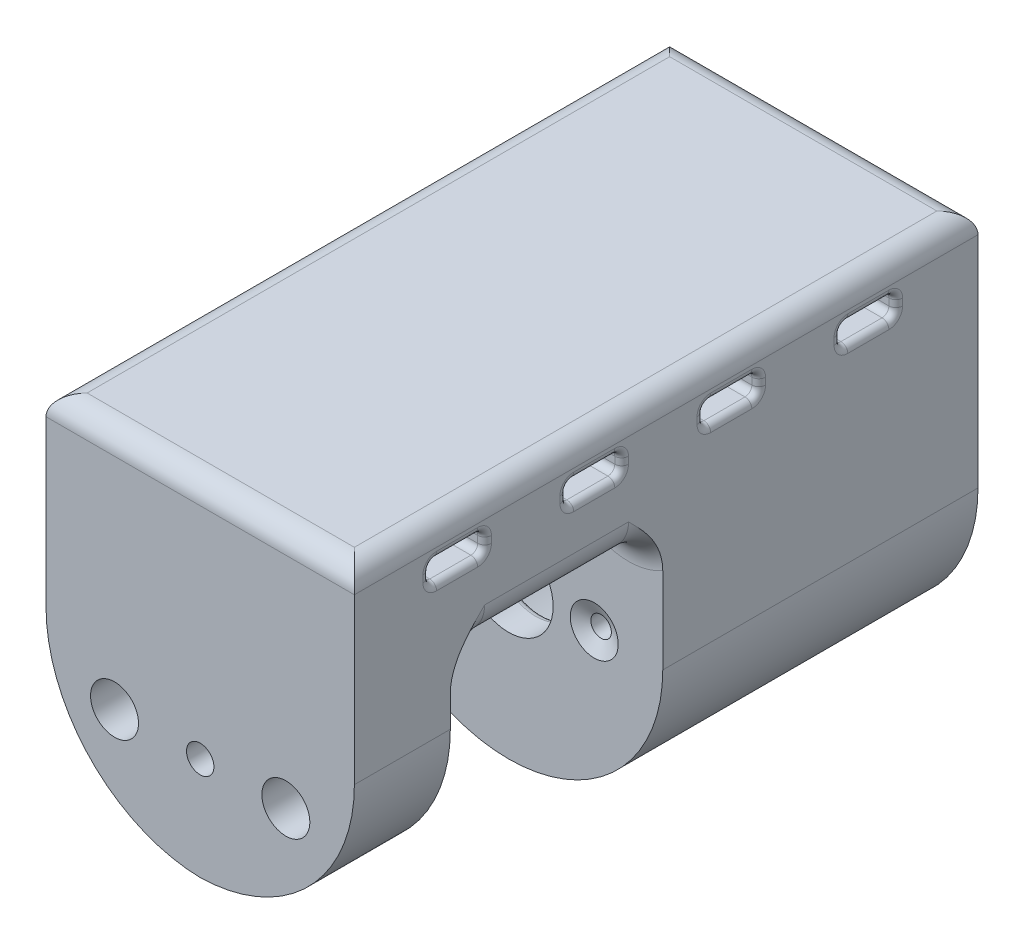
SolidWorks part; units mm, degrees
ref_plane "Płaszczyzna przednia" through (0, 0, 0) normal (0, 0, 1) x (1, 0, 0)
ref_plane "Płaszczyzna górna" through (0, 0, 0) normal (0, 1, 0) x (1, 0, 0)
ref_plane "Płaszczyzna prawa" through (0, 0, 0) normal (1, 0, 0) x (0, 0, -1)
sketch "Szkic1" plane through (0, 0, 0) normal (0, 0, 1) x (1, 0, 0)
  circle A1 centre (0, 0) radius 22.5
  dimension "D2" = 45
extrude "Dodanie-wyciągnięcie1" add sketch "Szkic1" along normal blind 5
sketch "Szkic2" plane through (0, 0, 5) normal (0, 0, 1) x (1, 0, 0)
  line L0 (-35.6914, 0) -> (33.7947, 0) construction
  circle A0 centre (0, 0) radius 6.5
  circle A1 centre (12.5, 0) radius 1.5
  circle A2 centre (-12.5, 0) radius 1.5
  dimension "D1" = 13
  dimension "D4" = 3
  dimension "D5" = 3
  dimension "D2" = 12.5
  dimension "D3" = 12.5
extrude "Wytnij-wyciągnięcie1" cut sketch "Szkic2" against normal up to next
chamfer "Sfazowanie1" distance 2 distance2 1 2 edges at (-11, 0, 5) (14, 0, 5) first distance on face at (-11, 0, 5)
sketch "Szkic4" plane through (0, 0, 0) normal (0, 0, -1) x (-1, 0, 0)
  circle A0 centre (0, 0) radius 18.7
  circle A1 centre (0, 0) radius 22.5
  dimension "D1" = 37.4
extrude "Dodanie-wyciągnięcie2" add sketch "Szkic4" along normal blind 41
fillet "Zaokrąglenie1" radius 1 1 edges at (-18.7, 0, 0)
fillet "Zaokrąglenie2" radius 1 1 edges at (6.5, 0, 0)
ref_plane "Płaszczyzna1" through (0, 35, 0) normal (0, 1, 0) x (1, 0, 0)
sketch "Szkic5" plane through (0, 35, 0) normal (0, 1, 0) x (1, 0, 0)
  line L1 (-22.5, 41) -> (22.5, 41)
  line L2 (-22.5, 41) -> (-22.5, -5)
  line L3 (-22.5, -5) -> (22.5, -5)
  line L4 (22.5, 41) -> (22.5, -5)
extrude "Dodanie-wyciągnięcie3" add sketch "Szkic5" against normal up to surface (35 mm away) up to face at (22.5, 0, 5)
sketch "Szkic7" plane through (0, 0, 5) normal (0, 0, 1) x (1, 0, 0)
  line L0 (-22.5, 21.2132) -> (-22.5, 35)
  line L1 (24.75, 35) -> (-24.75, 35) construction
  line L2 (-22.5, 0) -> (-22.5, 35) construction
  line L3 (-22.5, 35) -> (22.5, 35)
  line L4 (22.5, 0) -> (22.5, 35) construction
  line L5 (22.5, 35) -> (22.5, 21.2132)
  circle A0 centre (0, 0) radius 22.5 construction
  arc A1 (14.3182, 17.3563) -> (-14.3182, 17.3563) centre (0, 0) ccw
  arc A2 (22.5, 21.2132) -> (14.3182, 17.3563) centre (17.5, 21.2132) cw
  arc A3 (-22.5, 21.2132) -> (-14.3182, 17.3563) centre (-17.5, 21.2132) ccw
  point P18 (22.5, 0)
  point P21 (-22.5, 0)
  dimension "D1" = 5
extrude "Dodanie-wyciągnięcie4" add sketch "Szkic7" along normal blind 45
sketch "Szkic8" plane through (0, 35, 0) normal (0, 1, 0) x (1, 0, 0)
  line L0 (22.5, -50) -> (22.5, 41) construction
  line L1 (-22.5, -50) -> (22.5, -50)
  line L2 (-22.5, -50) -> (-22.5, -36)
  line L3 (-22.5, -36) -> (22.5, -36)
  line L4 (22.5, -50) -> (22.5, -36)
  dimension "D1" = 14
extrude "Dodanie-wyciągnięcie5" add sketch "Szkic8" against normal blind 50
sketch "Szkic10" plane through (0, 0, 36) normal (0, 0, -1) x (-1, 0, 0)
  circle A0 centre (0, 0) radius 4
  dimension "D1" = 8
extrude "Wytnij-wyciągnięcie3" cut sketch "Szkic10" against normal blind 10
sketch "Szkic11" plane through (0, 0, 46) normal (0, 0, -1) x (-1, 0, 0)
  circle A0 centre (0, 0) radius 2
  dimension "D1" = 4
extrude "Wytnij-wyciągnięcie4" cut sketch "Szkic11" against normal up to next
fillet "Zaokrąglenie5" radius 23 2 edges at (-22.5, -15, 43) (22.5, -15, 43)
fillet "Zaokrąglenie6" radius 5 6 edges at (-19.632, 16.6905, 5) (19.632, 16.6905, 5) (-19.632, 16.6905, 36) (0, 22.5, 36) (0, 22.5, 5) (19.632, 16.6905, 36)
sketch "Szkic12" plane through (22.5, 0, 0) normal (1, 0, 0) x (0, 0, -1)
  line L0 (-61.8696, 29) -> (66.432, 29) construction
  line L1 (24.75, 35) -> (-24.75, 35) construction
  line L2 (-50, 8) -> (-50, 35) construction
  line L3 (-38, 30.5) -> (-32, 30.5)
  line L4 (-39, 29.5) -> (-39, 28.5)
  line L5 (-38, 27.5) -> (-32, 27.5)
  line L6 (-31, 29.5) -> (-31, 28.5)
  line L7 (-39, 30.5) -> (-31, 27.5) construction
  line L8 (-39, 27.5) -> (-31, 30.5) construction
  line L9 (-19, 29.5) -> (-19, 28.5)
  line L10 (-18, 30.5) -> (-12, 30.5)
  line L11 (-11, 29.5) -> (-11, 28.5)
  line L12 (-18, 27.5) -> (-12, 27.5)
  line L13 (1, 29.5) -> (1, 28.5)
  line L14 (2, 30.5) -> (8, 30.5)
  line L15 (9, 29.5) -> (9, 28.5)
  line L16 (2, 27.5) -> (8, 27.5)
  line L17 (21, 29.5) -> (21, 28.5)
  line L18 (22, 30.5) -> (28, 30.5)
  line L19 (29, 29.5) -> (29, 28.5)
  line L20 (22, 27.5) -> (28, 27.5)
  line L21 (-39, 29.5) -> (-19, 29.5) construction
  arc A0 (-39, 28.5) -> (-38, 27.5) centre (-38, 28.5) ccw
  arc A1 (-38, 30.5) -> (-39, 29.5) centre (-38, 29.5) ccw
  arc A2 (-32, 30.5) -> (-31, 29.5) centre (-32, 29.5) cw
  arc A3 (-32, 27.5) -> (-31, 28.5) centre (-32, 28.5) ccw
  arc A4 (-18, 30.5) -> (-19, 29.5) centre (-18, 29.5) ccw
  arc A5 (-19, 28.5) -> (-18, 27.5) centre (-18, 28.5) ccw
  arc A6 (-12, 30.5) -> (-11, 29.5) centre (-12, 29.5) cw
  arc A7 (-12, 27.5) -> (-11, 28.5) centre (-12, 28.5) ccw
  arc A8 (2, 30.5) -> (1, 29.5) centre (2, 29.5) ccw
  arc A9 (1, 28.5) -> (2, 27.5) centre (2, 28.5) ccw
  arc A10 (8, 30.5) -> (9, 29.5) centre (8, 29.5) cw
  arc A11 (8, 27.5) -> (9, 28.5) centre (8, 28.5) ccw
  arc A12 (22, 30.5) -> (21, 29.5) centre (22, 29.5) ccw
  arc A13 (21, 28.5) -> (22, 27.5) centre (22, 28.5) ccw
  arc A14 (28, 30.5) -> (29, 29.5) centre (28, 29.5) cw
  arc A15 (28, 27.5) -> (29, 28.5) centre (28, 28.5) ccw
  point P4 (-35, 29)
  dimension "D5" = 1
  dimension "D1" = 6
  dimension "D2" = 8
  dimension "D3" = 3
  dimension "D4" = 15
  dimension "D7" = 20
  dimension "D6" = 4
extrude "Wytnij-wyciągnięcie5" cut sketch "Szkic12" against normal up to next
fillet "Zaokrąglenie7" radius 1 64 edges at (-22.5, 30.2071, -28.7071) (-22.5, 29, -29) (-22.5, 27.7929, -28.7071) (-22.5, 27.5, -25) (-22.5, 27.7929, -21.2929) (-22.5, 29, -21) (-22.5, 30.2071, -21.2929) (-22.5, 30.2071, -8.7071) (-22.5, 29, -9) (-22.5, 27.7929, -8.7071) (-22.5, 27.5, -5) (-22.5, 27.7929, -1.2929) (-22.5, 29, -1) (-22.5, 30.2071, -1.2929) (-22.5, 30.2071, 11.2929) (-22.5, 29, 11) (-22.5, 27.7929, 11.2929) (-22.5, 27.5, 15) (-22.5, 27.7929, 18.7071) (-22.5, 29, 19) (-22.5, 30.2071, 18.7071) (-22.5, 30.2071, 31.2929) (-22.5, 29, 31) (-22.5, 27.7929, 31.2929) (-22.5, 27.5, 35) (-22.5, 27.7929, 38.7071) (-22.5, 29, 39) (-22.5, 30.2071, 38.7071) (22.5, 30.2071, 31.2929) (22.5, 29, 31) (22.5, 27.7929, 31.2929) (22.5, 27.5, 35) (22.5, 27.7929, 38.7071) (22.5, 29, 39) (22.5, 30.2071, 38.7071) (22.5, 30.2071, 11.2929) (22.5, 29, 11) (22.5, 27.7929, 11.2929) (22.5, 27.5, 15) (22.5, 27.7929, 18.7071) (22.5, 29, 19) (22.5, 30.2071, 18.7071) (22.5, 30.2071, -8.7071) (22.5, 29, -9) (22.5, 27.7929, -8.7071) (22.5, 27.5, -5) (22.5, 27.7929, -1.2929) (22.5, 29, -1) (22.5, 30.2071, -1.2929) (22.5, 30.2071, -28.7071) (22.5, 29, -29) (22.5, 27.7929, -28.7071) (22.5, 27.5, -25) (22.5, 27.7929, -21.2929) (22.5, 29, -21) (22.5, 30.2071, -21.2929) (-22.5, 30.5, -25) (-22.5, 30.5, -5) (-22.5, 30.5, 15) (-22.5, 30.5, 35) (22.5, 30.5, 35) (22.5, 30.5, 15) (22.5, 30.5, -5) (22.5, 30.5, -25)
fillet "Zaokrąglenie8" radius 3 4 edges at (0, 35, -41) (22.5, 35, 4.5) (0, 35, 50) (-22.5, 35, 4.5)
sketch "Szkic13" plane through (0, 0, 50) normal (0, 0, 1) x (1, 0, 0)
  circle A0 centre (12.5, 0) radius 3.5
  circle A1 centre (-12.5, 0) radius 3.5
  dimension "D1" = 7
  dimension "D2" = 7
extrude "Wytnij-wyciągnięcie6" cut sketch "Szkic13" against normal up to next
